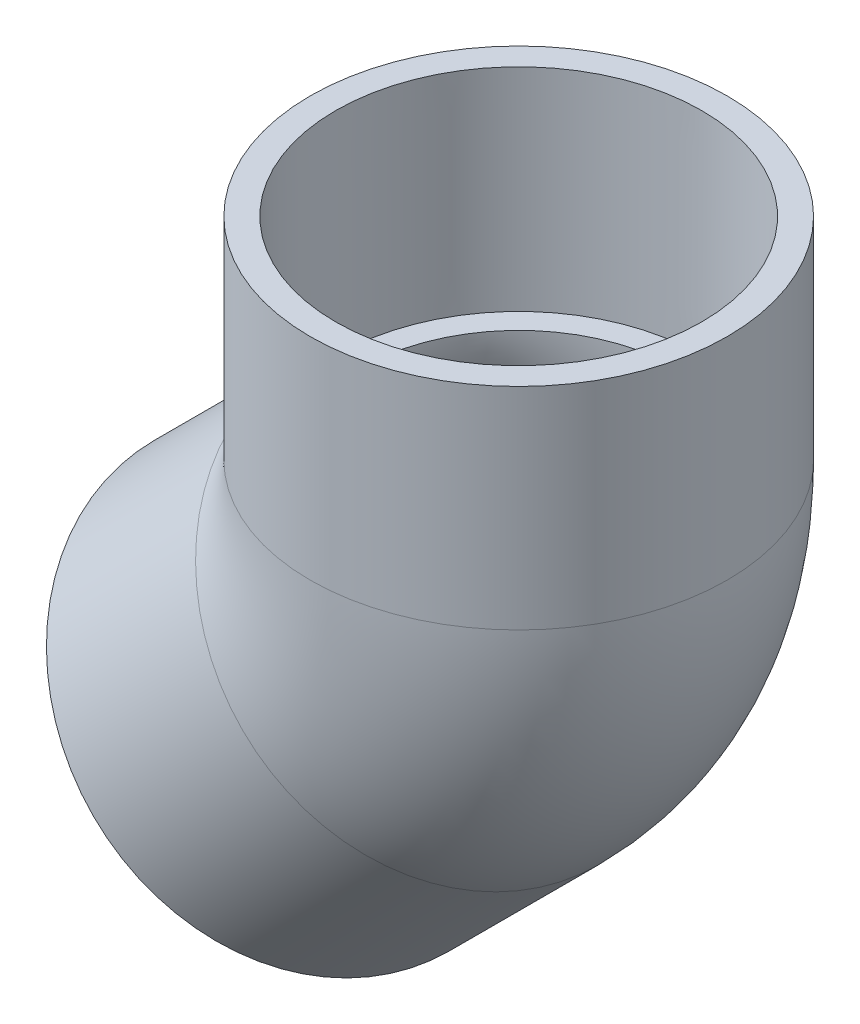
SolidWorks part; units mm, degrees
ref_plane "Front Plane" through (0, 0, 0) normal (0, 0, 1) x (1, 0, 0)
ref_plane "Top Plane" through (0, 0, 0) normal (0, 1, 0) x (1, 0, 0)
ref_plane "Right Plane" through (0, 0, 0) normal (1, 0, 0) x (0, 0, -1)
sketch "ElbowArc" plane through (0, 0, 0) normal (0, 0, 1) x (1, 0, 0)
  line L0 (-35.921, -35.921) -> (0, 0) construction
  line L1 (0, 0) -> (0, 50.8) construction
  line L2 (-11.2253, -11.2253) -> (0, 0) construction
  line L3 (0, 0) -> (0, 15.875) construction
  line L4 (-60.3361, -11.506) -> (-11.506, -60.3361) construction
  line L5 (-32.4995, 10.0489) -> (-57.3569, -14.4852) construction
  line L6 (-32.4995, 10.0489) -> (10.0489, -32.4995) construction
  line L7 (10.0489, -32.4995) -> (-14.4852, -57.3569) construction
  line L8 (-57.3569, -14.4852) -> (-14.4852, -57.3569) construction
  line L9 (-34.5281, 50.8) -> (34.5281, 50.8) construction
  line L10 (-30.3149, 50.8) -> (30.3149, 50.8) construction
  line L11 (30.3149, 50.8) -> (30.0863, 15.875) construction
  line L12 (30.0863, 15.875) -> (-30.0863, 15.875) construction
  line L13 (-30.0863, 15.875) -> (-30.3149, 50.8) construction
  line L14 (-29.7875, 7.3369) -> (7.3369, -29.7875) construction
  line L18 (-26.2509, 15.875) -> (26.2509, 15.875) construction
  arc A0 (0, 15.875) -> (-11.2253, -11.2253) centre (-38.3256, 15.875) cw construction
  dimension "BendRadius" = 38.3256
  dimension "D1" = 45
  dimension "BendAngle" = 50.8
  dimension "J" = 15.875
  dimension "M" = 69.0563
  dimension "OD A" = 60.6298
  dimension "OD B" = 60.1726
  dimension "ID" = 52.5018
sketch "Sketch1" plane through (0, 0, 0) normal (0, 0, 1) x (1, 0, 0)
  line L0 (-35.921, -35.921) -> (0, 0) construction
  line L1 (-35.921, -35.921) -> (0, 0) construction
  line L3 (-11.506, -60.3361) -> (13.1898, -35.6404)
  line L4 (-11.506, -60.3361) -> (-14.4852, -57.3569)
  line L5 (-14.4852, -57.3569) -> (10.0489, -32.4995)
  line L6 (13.1898, -35.6404) -> (10.0489, -32.4995)
revolve "Revolve1" add sketch "Sketch1" angle 360 about L1
sketch "Sketch2" plane through (0, 0, 0) normal (0, 0, 1) x (1, 0, 0)
  line L0 (30.3149, 50.8) -> (30.0863, 15.875)
  line L1 (30.0863, 15.875) -> (34.5281, 15.875)
  line L2 (34.5281, 15.875) -> (34.5281, 50.8)
  line L3 (34.5281, 50.8) -> (30.3149, 50.8)
  line L4 (0, 0) -> (0, 50.8) construction
  line L5 (0, 0) -> (0, 50.8) construction
revolve "Revolve2" add sketch "Sketch2" angle 360 about L5
sketch "Sketch3" plane through (-11.2253, -11.2253, 0) normal (0.7071, 0.7071, 0) x (0, 0, -1)
  circle A0 centre (0, 0) radius 26.2509
  circle A1 centre (0, 0) radius 34.5281
sketch "Sketch4" plane through (0, 0, 0) normal (0, 0, 1) x (1, 0, 0)
  line L0 (-35.921, -35.921) -> (0, 0) construction
  line L1 (0, 0) -> (0, 50.8) construction
  line L2 (-35.921, -35.921) -> (-11.2253, -11.2253) construction
  line L3 (0, 15.875) -> (0, 50.8) construction
  arc A0 (-11.2253, -11.2253) -> (0, 15.875) centre (-38.3256, 15.875) ccw
sweep "Sweep1" add profiles "Sketch3" path "Sketch4"
other "CPoint1" parameters "Diameter"=50.8, "StubLength"=228.6
ref_axis "Axis1" through (0, 25.875, 0) along (0, -1, 0)
other "CPoint2" parameters "Diameter"=50.8, "StubLength"=76.2
ref_axis "Axis2" through (-18.2964, -18.2964, 0) along (0.7071, 0.7071, 0)
other "RPoint1"
